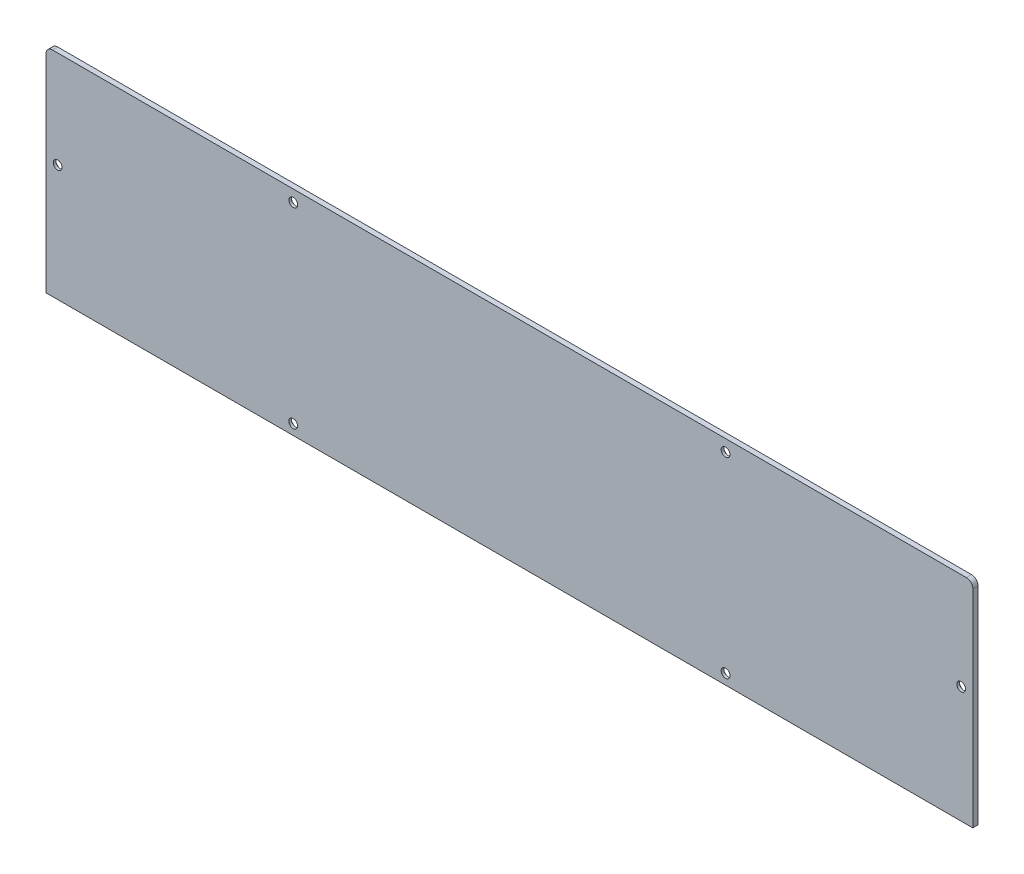
SolidWorks part; units mm, degrees
material "6061 合金"
ref_plane "前视基准面" through (0, 0, 0) normal (0, 0, 1) x (1, 0, 0)
ref_plane "上视基准面" through (0, 0, 0) normal (0, 1, 0) x (1, 0, 0)
ref_plane "右视基准面" through (0, 0, 0) normal (1, 0, 0) x (0, 0, -1)
sketch "草图1" plane through (0, 0, 222.7245) normal (0, 0, -1) x (-1, 0, 0)
  line L0 (282.7502, -10) -> (-76.2519, -10) construction
  line L1 (-76.2519, 70) -> (-76.2519, -2.5) construction
  line L2 (282.7502, -8.05) -> (282.7502, 70) construction
  line L4 (-76.2519, -10) -> (282.7502, -10)
  line L5 (282.7502, 70) -> (282.7502, -10)
  line L6 (279.7502, 73) -> (-73.2519, 73)
  line L7 (-76.2519, -10) -> (-76.2519, 70)
  arc A2 (282.7502, 70) -> (279.7502, 73) centre (279.7502, 70) ccw
  arc A3 (-73.2519, 73) -> (-76.2519, 70) centre (-73.2519, 70) ccw
  arc A4 (-73.2519, 73) -> (-76.2519, 70) centre (-73.2519, 70) ccw construction
  arc A5 (282.7502, 70) -> (279.7502, 73) centre (279.7502, 70) ccw construction
extrude "凸台-拉伸1" add sketch "草图1" along normal blind 2
sketch "草图2" plane through (0, 0, 220.7245) normal (0, 0, 1) x (1, 0, 0)
  line L0 (71.2519, 35) -> (71.2519, 68) construction
  line L1 (71.2519, 68) -> (-19.7492, 68) construction
  line L2 (-19.7492, 68) -> (-186.7492, 68) construction
  line L3 (-186.7492, 68) -> (-277.7502, 68) construction
  line L4 (-277.7502, 68) -> (-277.7502, 35) construction
  circle A4 centre (-277.7502, 35) radius 1.25
  circle A5 centre (-186.7492, 68) radius 1.25
  circle A6 centre (-19.7492, 68) radius 1.25
  circle A7 centre (71.2519, 35) radius 1.25
  circle A11 centre (-277.7502, 35) radius 1.0974 construction
  circle A12 centre (-186.7492, 68) radius 1.25 construction
  circle A13 centre (-19.7492, 68) radius 1.25 construction
  circle A14 centre (71.2519, 35) radius 1.25 construction
hole_wizard "打孔尺寸(%根据)内六角圆柱头螺钉的类型2" positions "3D草图1" profile "草图3" counterbore size "M3" standard "GB"
sketch3d "3D草图1"
  point P0 (71.2519, 35, 220.7245)
  point P3 (-19.7492, 68, 220.7245)
  point P6 (-186.7492, 68, 220.7245)
  point P9 (-277.7502, 35, 220.7245)
sketch "草图3" plane through (71.2519, 35, 220.7245) normal (1, 0, 0) x (0, 1, 0)
  line L0 (0, 0) -> (0, 8.5215)
  line L1 (0, 8.5215) -> (1.7, 7.5)
  line L2 (1.7, 7.5) -> (1.7, 1)
  line L3 (1.7, 1) -> (3, 1)
  line L4 (3, 1) -> (3, 0)
  line L5 (3, 0) -> (0, 0)
  line L10 (0, 8.5215) -> (-1.7, 7.5) construction
  line L11 (0, -6.35) -> (0, 107.95) construction
  dimension "孔直径" = 3.4
  dimension "孔深度" = 7.5
  dimension "柱形沉头孔直径" = 6
  dimension "柱形沉头孔深度" = 1
  dimension "导头角度" = 118
sketch "草图4" plane through (0, 0, 220.7245) normal (0, 0, -1) x (-1, 0, 0)
  line L4 (-76.2519, 70) -> (-76.2519, -10)
  line L5 (-76.2519, -10) -> (282.7502, -10)
  line L6 (282.7502, -10) -> (282.7502, 70)
  line L7 (279.7502, 73) -> (-73.2519, 73)
  line L8 (-76.2519, 70) -> (-76.2519, -10)
  line L10 (282.7502, -10) -> (282.7502, 70)
  line L11 (279.7502, 73) -> (-73.2519, 73)
  line L13 (282.2502, -10) -> (282.2502, 70)
  line L14 (279.7502, 72.5) -> (-73.2519, 72.5)
  line L15 (-75.7519, 70) -> (-75.7519, -10)
  line L16 (282.2502, -10) -> (282.7502, -10)
  line L17 (-76.2519, -10) -> (-75.7519, -10)
  arc A2 (282.7502, 70) -> (279.7502, 73) centre (279.7502, 70) ccw
  arc A3 (-73.2519, 73) -> (-76.2519, 70) centre (-73.2519, 70) ccw
  arc A4 (282.7502, 70) -> (279.7502, 73) centre (279.7502, 70) ccw
  arc A5 (-73.2519, 73) -> (-76.2519, 70) centre (-73.2519, 70) ccw
  arc A6 (282.2502, 70) -> (279.7502, 72.5) centre (279.7502, 70) ccw
  arc A8 (-73.2519, 72.5) -> (-75.7519, 70) centre (-73.2519, 70) ccw
  dimension "D1" = 0
  dimension "D3" = 0.5
extrude "切除-拉伸1" cut sketch "草图4" against normal through all
hole_wizard "打孔尺寸(%根据)内六角圆柱头螺钉的类型2" positions "3D草图2" profile "草图5" counterbore size "M3" standard "GB"
sketch3d "3D草图2"
  point P0 (-19.7492, -6, 195.7245)
  point P3 (-186.7492, -6, 195.7245)
sketch "草图5" plane through (-19.7492, -6, 220.7245) normal (1, 0, 0) x (0, 1, 0)
  line L0 (0, 0) -> (0, 20.5215)
  line L1 (0, 20.5215) -> (1.7, 19.5)
  line L2 (1.7, 19.5) -> (1.7, 1)
  line L3 (1.7, 1) -> (3, 1)
  line L4 (3, 1) -> (3, 0)
  line L5 (3, 0) -> (0, 0)
  line L6 (0, 20.5215) -> (-1.7, 19.5) construction
  line L7 (0, -6.35) -> (0, 107.95) construction
  dimension "孔直径" = 3.4
  dimension "孔深度" = 19.5
  dimension "柱形沉头孔直径" = 6
  dimension "柱形沉头孔深度" = 1
  dimension "导头角度" = 118
